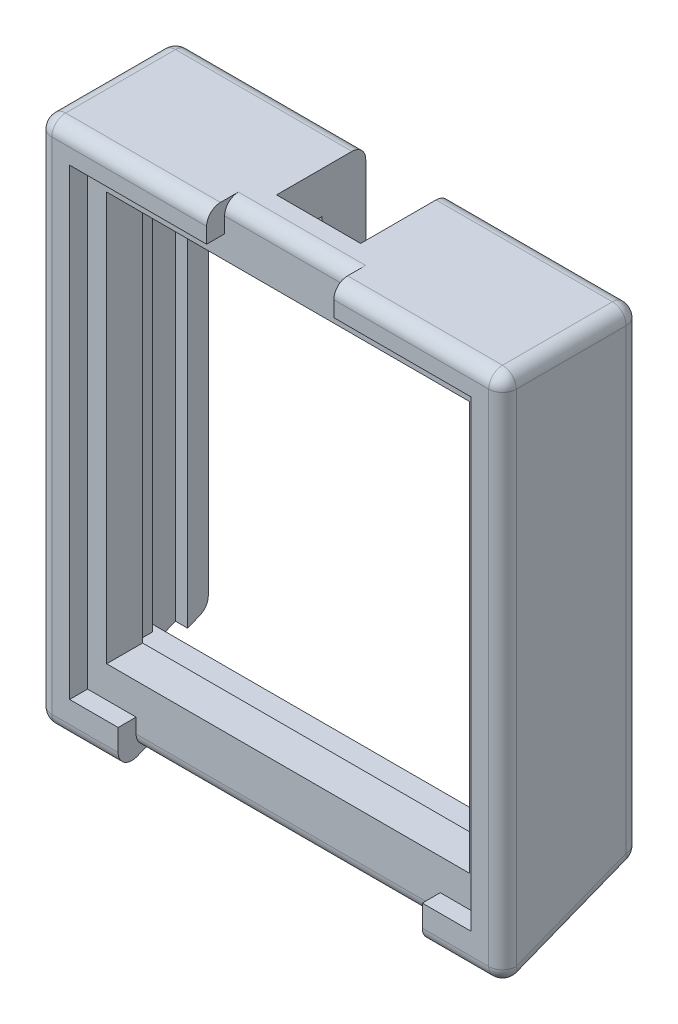
SolidWorks part; units mm, degrees
ref_plane "Front Plane" through (0, 0, 0) normal (0, 0, 1) x (1, 0, 0)
ref_plane "Top Plane" through (0, 0, 0) normal (0, 1, 0) x (1, 0, 0)
ref_plane "Right Plane" through (0, 0, 0) normal (1, 0, 0) x (0, 0, -1)
ref_plane "Plane1" through (0, -6.854, -2.6902) normal (0, 0.9309, 0.3654) x (1, 0, 0)
ref_plane "Plane2" through (0, 27.52, 0) normal (0, 1, 0) x (1, 0, 0)
sketch "Sketch3" plane through (0, 0, 0) normal (0, 1, 0) x (1, 0, 0)
  line L0 (-14.43, 1.8) -> (-14.43, 0.3)
  line L1 (-14.43, 0.3) -> (-15.3, 0.3)
  line L2 (-15.3, 0.3) -> (-15.3, -1.95)
  line L3 (-15.3, -1.95) -> (-14.23, -1.95)
  line L6 (-14.23, -1.95) -> (-14.23, -3.55)
  line L7 (-14.23, -3.55) -> (-13.13, -3.55)
  line L8 (-13.13, -3.55) -> (-13.13, -6.85)
  line L9 (-13.13, -6.85) -> (-14.51, -6.85)
  line L10 (-14.51, -6.85) -> (-14.51, -8.15)
  line L11 (-14.51, -8.15) -> (-16.8, -8.15)
  line L12 (-16.8, -8.15) -> (-16.8, 1.8)
  line L13 (-16.8, 1.8) -> (-14.43, 1.8)
  line L14 (-15, 0) -> (15, 0) construction
  line L15 (-15, -1.65) -> (-15, 0) construction
  line L16 (-15, -1.65) -> (15, -1.65) construction
  line L17 (-13.91, -7.15) -> (13.91, -7.15) construction
  line L18 (-13.93, -4.65) -> (-13.93, -6.15) construction
  line L19 (-13.91, -8.65) -> (-13.91, -7.15) construction
  line L20 (-13.91, -8.65) -> (13.91, -8.65) construction
  line L21 (0, 0) -> (0, -15.6727) construction
  line L22 (16.8, 1.8) -> (14.43, 1.8)
  line L23 (16.8, -8.15) -> (16.8, 1.8)
  line L24 (14.51, -8.15) -> (16.8, -8.15)
  line L25 (14.51, -6.85) -> (14.51, -8.15)
  line L26 (13.13, -6.85) -> (14.51, -6.85)
  line L27 (13.13, -3.55) -> (13.13, -6.85)
  line L28 (14.23, -3.55) -> (13.13, -3.55)
  line L29 (14.23, -1.95) -> (14.23, -3.55)
  line L30 (15.3, -1.95) -> (14.23, -1.95)
  line L31 (15.3, 0.3) -> (15.3, -1.95)
  line L32 (14.43, 0.3) -> (15.3, 0.3)
  line L33 (14.43, 1.8) -> (14.43, 0.3)
  dimension "D1" = 0.3
  dimension "D2" = 0.3
  dimension "D3" = 0.3
  dimension "D6" = 0.3
  dimension "D8" = 0.3
  dimension "D9" = 0.6
  dimension "D10" = 0.5
  dimension "D11" = 1.5
  dimension "D12" = 1.5
  dimension "D13" = 0.5
  dimension "D4" = 0.8
  dimension "D5" = 0.3
extrude "Boss-Extrude1" add sketch "Sketch3" along normal up to surface (27.52 mm away) and the other way up to surface up to plane "Plane2" other way up to plane "Plane1"
sketch "Sketch4" plane through (0, 0, 0) normal (1, 0, 0) x (0, 0, -1)
  line L0 (1.8, 27.52) -> (-8.15, 27.52)
  line L1 (-8.15, 27.52) -> (-8.15, 25.4)
  line L2 (-8.15, 27.52) -> (-8.15, -11.1088) construction
  line L3 (-8.15, 25.4) -> (-6.85, 25.4)
  line L4 (-6.85, 27.52) -> (-6.85, -10.5985) construction
  line L5 (-6.85, 25.4) -> (-6.85, 23.755)
  line L6 (-6.85, 23.755) -> (-3.55, 23.755)
  line L7 (-3.55, 27.52) -> (-3.55, -9.3033) construction
  line L8 (-3.55, 23.755) -> (-3.55, 24.52)
  line L9 (-3.55, 27.52) -> (-3.55, -9.3033) construction
  line L11 (-3.55, -6.56) -> (-1.95, -6.56)
  line L14 (1.8, 27.52) -> (1.8, -7.2034) construction
  line L15 (1.8, 22.1) -> (1.8, 27.52)
  line L16 (-3.55, 24.52) -> (-1.35, 24.52)
  line L17 (-1.35, 24.52) -> (-1.35, 22.1)
  line L18 (-1.35, 22.1) -> (0.3, 22.1)
  line L19 (0.3, 22.1) -> (0.3, 20.1)
  line L20 (-6.15, 24.555) -> (-4.65, 24.555) construction
  line L21 (-1.65, 21.8) -> (0, 21.8) construction
  line L22 (-8.65, 24.8) -> (-7.15, 24.8) construction
  line L23 (-1.95, 27.52) -> (-1.95, -8.6753) construction
  line L24 (-8.15, -8.07) -> (-8.15, -11.1088)
  line L25 (-8.15, -11.1088) -> (-1.95, -8.6753)
  line L26 (-1.95, -8.6753) -> (-1.95, -6.56)
  line L29 (-3.55, -6.56) -> (-3.55, -5.795)
  line L30 (-3.55, -5.795) -> (-6.85, -5.795)
  line L31 (-6.85, -5.795) -> (-6.85, -8.07)
  line L32 (-6.85, 27.52) -> (-6.85, -10.5985) construction
  line L33 (-6.85, -8.07) -> (-8.15, -8.07)
  line L34 (-8.65, -7.47) -> (-7.15, -7.47) construction
  line L35 (-4.65, -6.595) -> (-6.15, -6.595) construction
  line L36 (0.3, 27.52) -> (0.3, -7.7922) construction
  line L37 (0.3, 20.1) -> (1.8, 20.1)
  line L38 (1.8, 20.1) -> (1.8, 22.1)
  dimension "D2" = 0.3
  dimension "D3" = 0.3
  dimension "D8" = 0.3
  dimension "D4" = 0.8
  dimension "D5" = 0.6
  dimension "D6" = 0.6
  dimension "D7" = 0.8
  dimension "D9" = 2
extrude "Boss-Extrude2" add sketch "Sketch4" along normal up to surface and the other way up to surface up to face at (16.8, 9.182, 3.175) other way up to face at (-16.8, 9.182, 3.175)
fillet "Fillet1" radius 1 2 edges at (0, -8.6753, 1.95) (0, -11.1088, 8.15)
sketch "Sketch5" plane through (0, 0, 8.15) normal (0, 0, 1) x (1, 0, 0)
  line L0 (4.6, 24.8) -> (4.6, 25.7)
  line L1 (4.6, 25.7) -> (-4.6, 25.7) construction
  line L2 (-4.6, 25.7) -> (-4.6, 24.8)
  line L3 (-4.6, 24.8) -> (4.6, 24.8)
  line L4 (-4.6, 25.7) -> (-4.6, 27.52)
  line L5 (-16.8, 27.52) -> (16.8, 27.52) construction
  line L6 (-4.6, 27.52) -> (4.6, 27.52)
  line L7 (4.6, 27.52) -> (4.6, 25.7)
  line L8 (13.91, -7.47) -> (13.91, 24.8)
  line L9 (13.91, 24.8) -> (4, 24.8)
  line L10 (4, 24.8) -> (4, 25.1)
  line L11 (4, 25.1) -> (-4, 25.1)
  line L12 (-4, 25.1) -> (-4, 24.8)
  line L13 (-4, 24.8) -> (-13.91, 24.8)
  line L14 (-13.91, 24.8) -> (-13.91, -7.47)
  line L15 (-13.91, -7.47) -> (13.91, -7.47)
  line L16 (13.91, -7.47) -> (13.91, 24.8) construction
  line L17 (13.91, 24.8) -> (4, 24.8) construction
  line L18 (4, 24.8) -> (4, 25.1) construction
  line L19 (4, 25.1) -> (-4, 25.1) construction
  line L20 (-4, 25.1) -> (-4, 24.8) construction
  line L21 (-4, 24.8) -> (-13.91, 24.8) construction
  line L22 (-13.91, 24.8) -> (-13.91, -7.47) construction
  line L23 (-13.91, -7.47) -> (13.91, -7.47) construction
  line L24 (-11, -8.07) -> (-11, -10.642)
  line L25 (14.51, -8.07) -> (-14.51, -8.07) construction
  line L26 (-11, -10.642) -> (11, -10.642)
  line L27 (-11, -8.07) -> (11, -8.07)
  line L28 (0, 0) -> (0, -15.5564) construction
  line L29 (-10, -7.47) -> (-10, -10.77) construction
  line L30 (-16.8, -10.642) -> (16.8, -10.642) construction
  line L31 (11, -8.07) -> (11, -10.642)
  point P30 (0, -8.07)
  point P31 (0, -10.642)
  dimension "D3" = 1
  dimension "D2" = 0.6
extrude "Cut-Extrude1" cut sketch "Sketch5" against normal up to surface (1.3 mm away) up to face at (0, 8.98, 6.85)
chamfer "Chamfer1" distance 0.7 angle 45 4 edges at (0, 23.755, 3.55) (13.13, 8.98, 3.55) (0, -5.795, 3.55) (-13.13, 8.98, 3.55)
fillet "Fillet2" radius 1 17 edges at (-16.8, -8.8881, 2.4923) (-16.8, -10.4683, 7.7133) (16.8, -8.8881, 2.4923) (16.8, -10.4683, 7.7133) (16.8, 27.52, 3.175) (10.7, 27.52, 8.15) (-10.7, 27.52, 8.15) (-16.8, 27.52, 3.175) (0, 27.52, -1.8) (-15.615, -7.2034, -1.8) (15.615, -7.2034, -1.8) (16.8, 10.1583, -1.8) (-16.8, 10.1583, -1.8) (-16.8, 8.939, 8.15) (16.8, 8.939, 8.15) (0, 27.52, 6.85) (0, -10.596, 6.85)
sketch "Sketch6" plane through (0, 0, -1.8) normal (0, 0, -1) x (-1, 0, 0)
  line L0 (0, 26.6333) -> (0, 0) construction
  line L1 (3.04, 0.0257) -> (-3.04, 0.0257)
  line L2 (-3.04, 0.0257) -> (-3.04, 27.52)
  line L3 (-3.04, 27.52) -> (3.04, 27.52)
  line L4 (-15.8, 27.52) -> (15.8, 27.52) construction
  line L6 (3.04, 0.0257) -> (3.04, 27.52)
  point P12 (0, 27.52)
  point P13 (0, 0.0257)
  dimension "D1" = 3.04
extrude "Cut-Extrude2" cut sketch "Sketch6" against normal up to surface (6.45 mm away)
chamfer "Chamfer3" distance 0.5 angle 45 4 edges at (14.23, 8.98, 1.95) (-14.23, 8.98, 1.95) (9.17, 22.1, 1.35) (-9.17, 22.1, 1.35)
equation "\"offset\"= .3mm"
equation "\"D1@Sketch3\"=\"offset\""
equation "\"D2@Sketch3\"=\"offset\""
equation "\"D3@Sketch3\"=\"offset\""
equation "\"D6@Sketch3\"=\"offset\""
equation "\"D8@Sketch3\"=\"offset\""
equation "\"D9@Sketch3\"=\"offset\"*2"
equation "\"D1@Plane2\"=3+\"offset\""
equation "\"led apnel overlap\"= .8"
equation "\"clearance\"=0.5"
equation "\"D2@Sketch4\"=\"offset\""
equation "\"D4@Sketch4\"=\"led apnel overlap\""
equation "\"D5@Sketch4\"=\"offset\"*2"
equation "\"D6@Sketch4\"=\"offset\"*2"
equation "\"D7@Sketch4\"=\"led apnel overlap\""
equation "\"D2@Sketch5\"=\"offset\"*2"
equation "\"D1@Sketch6\" = .1in + \"clearance\""
equation "\"D5@Sketch3\"=\"offset\""
equation "\"D3@Sketch4\"=\"offset\""
equation "\"D8@Sketch4\"=\"offset\""
equation "\"D1@Sketch4\"=\"offset\""
